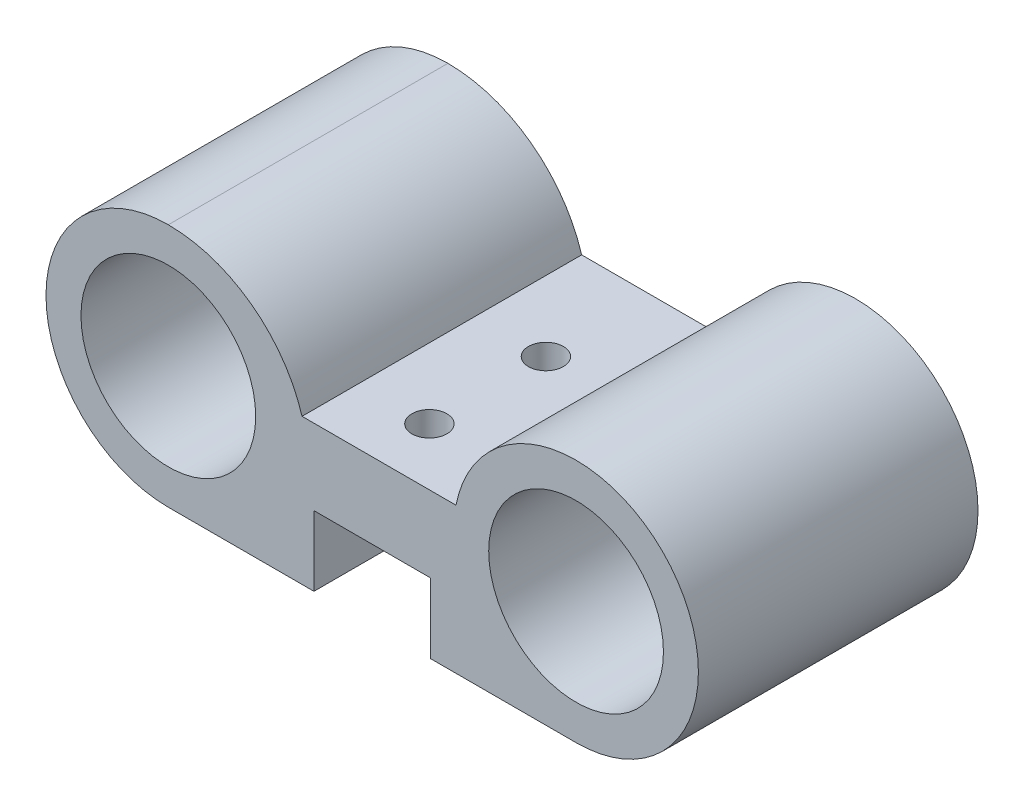
SolidWorks part; units mm, degrees
ref_plane "Front Plane" through (0, 0, 0) normal (0, 0, 1) x (1, 0, 0)
ref_plane "Top Plane" through (0, 0, 0) normal (0, 1, 0) x (1, 0, 0)
ref_plane "Right Plane" through (0, 0, 0) normal (1, 0, 0) x (0, 0, -1)
sketch "Sketch2" plane through (0, 0, 0) normal (0, 0, 1) x (1, 0, 0)
  line L0 (-17.5, 4.5) -> (17.5, 4.5) construction
  line L7 (-17.5, -6) -> (-5, -6)
  line L10 (-6.0218, 6.5) -> (-4.5, 6.5)
  line L14 (-4.5, 6.5) -> (7.1922, 6.5)
  line L19 (5, -6) -> (5, 0)
  line L20 (5, 0) -> (-5, 0)
  line L21 (-5, 0) -> (-5, -6)
  line L23 (5, -6) -> (17.5, -6)
  circle A0 centre (-17.5, 4.5) radius 7.5
  circle A1 centre (17.5, 4.5) radius 7.5
  arc A2 (-17.5, 15) -> (-17.5, -6) centre (-17.5, 4.5) ccw
  arc A3 (17.5, -6) -> (17.5, 15) centre (17.5, 4.5) ccw
  arc A4 (-17.5, 15) -> (-6.0218, 6.5) centre (-17.5, 3) cw
  arc A5 (17.5, 15) -> (7.1922, 6.5) centre (17.5, 4.5) ccw
  point P0 (0, 0)
  point P2 (0, 0)
  point P10 (0, 4.5)
  dimension "D1" = 15
  dimension "D3" = 3
  dimension "D9" = 12
  dimension "D2" = 35
  dimension "D4" = 12.5
  dimension "D5" = 10
  dimension "D6" = 6
extrude "Boss-Extrude1" add sketch "Sketch2" along normal blind 24
sketch "Sketch4" plane through (0, 0, 0) normal (0, -1, 0) x (1, 0, 0)
  line L0 (-5, 0) -> (5, 0) construction
  circle A0 centre (0, 9.091) radius 1.5
  circle A1 centre (0, 19.091) radius 1.5
  dimension "D1" = 3
  dimension "D2" = 9.091
  dimension "D3" = 10
extrude "Cut-Extrude1" cut sketch "Sketch4" against normal blind 10
